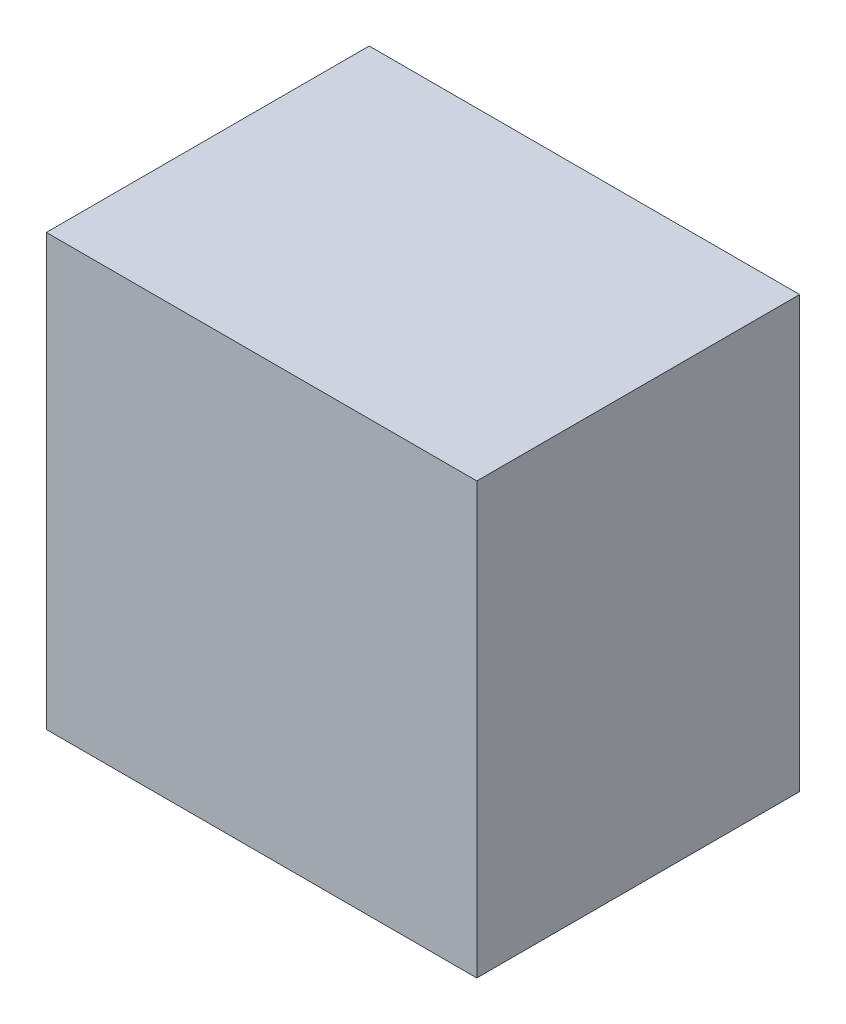
SolidWorks part; units mm, degrees
ref_plane "Front Plane" through (0, 0, 0) normal (0, 0, 1) x (1, 0, 0)
ref_plane "Top Plane" through (0, 0, 0) normal (0, 1, 0) x (1, 0, 0)
ref_plane "Right Plane" through (0, 0, 0) normal (1, 0, 0) x (0, 0, -1)
sketch "Sketch1" plane through (0, 0, 0) normal (0, 0, 1) x (1, 0, 0)
  line L1 (0, 0) -> (40, 0)
  line L2 (0, 0) -> (0, 40)
  line L3 (0, 40) -> (40, 40)
  line L4 (40, 0) -> (40, 40)
extrude "Boss-Extrude1" add sketch "Sketch1" along normal blind 15 and the other way blind 15
sketch "Sketch2" plane through (0, 0, 0) normal (0, 0, 1) x (1, 0, 0)
  line L1 (0, 0) -> (10, 0)
  line L2 (0, 0) -> (0, 10)
  line L3 (0, 10) -> (10, 10)
  line L4 (10, 0) -> (10, 10)
extrude "Cut-Extrude1" cut sketch "Sketch2" against normal blind 5 and the other way blind 12
